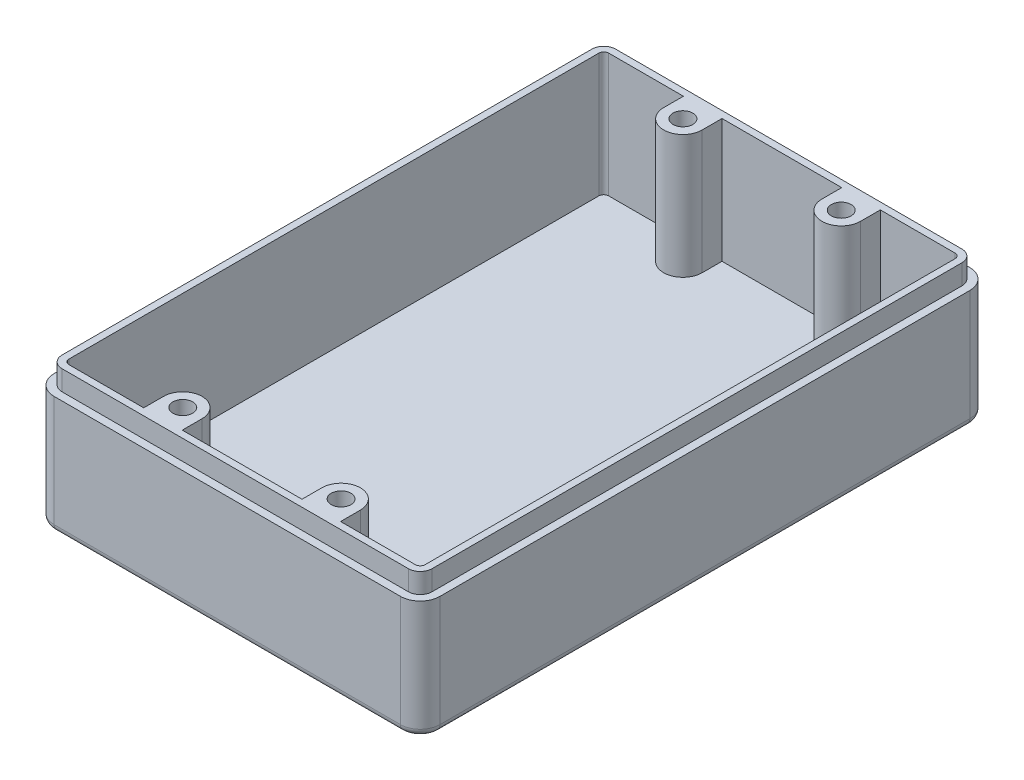
SolidWorks part; units mm, degrees
ref_plane "Plan de face" through (0, 0, 0) normal (0, 0, 1) x (1, 0, 0)
ref_plane "Plan de dessus" through (0, 0, 0) normal (0, 1, 0) x (1, 0, 0)
ref_plane "Plan de droite" through (0, 0, 0) normal (1, 0, 0) x (0, 0, -1)
sketch "Esquisse1" plane through (0, 0, 0) normal (0, 1, 0) x (1, 0, 0)
  line L1 (-39, 0) -> (39, 0)
  line L2 (-39, 0) -> (-39, 115.1)
  line L3 (-39, 115.1) -> (39, 115.1)
  line L4 (39, 0) -> (39, 115.1)
  dimension "D1" = 78
  dimension "D2" = 115.1
extrude "Top_Volume" add sketch "Esquisse1" along normal blind 28
fillet "Corner_Radius" radius 4 4 edges at (-39, 14, -115.1) (39, 14, -115.1) (39, 14, 0) (-39, 14, 0)
shell "Inside_Hole" thickness 3 removed face at (0, 28, -57.55)
sketch "Esquisse2" plane through (0, 28, 0) normal (0, 1, 0) x (1, 0, 0)
  line L8 (35, 113.5) -> (-35, 113.5)
  line L9 (-37.4, 111.1) -> (-37.4, 4)
  line L10 (-35, 1.6) -> (35, 1.6)
  line L11 (37.4, 4) -> (37.4, 111.1)
  line L12 (35, 113.5) -> (-35, 113.5)
  line L13 (-37.4, 111.1) -> (-37.4, 4)
  line L14 (-35, 1.6) -> (35, 1.6)
  line L15 (37.4, 4) -> (37.4, 111.1)
  arc A8 (-35, 113.5) -> (-37.4, 111.1) centre (-35, 111.1) ccw
  arc A9 (-35, 113.5) -> (-37.4, 111.1) centre (-35, 111.1) ccw
  arc A10 (-37.4, 4) -> (-35, 1.6) centre (-35, 4) ccw
  arc A11 (-37.4, 4) -> (-35, 1.6) centre (-35, 4) ccw
  arc A12 (35, 1.6) -> (37.4, 4) centre (35, 4) ccw
  arc A13 (35, 1.6) -> (37.4, 4) centre (35, 4) ccw
  arc A14 (37.4, 111.1) -> (35, 113.5) centre (35, 111.1) ccw
  arc A15 (37.4, 111.1) -> (35, 113.5) centre (35, 111.1) ccw
  dimension "D1" = 1.6
extrude "Border_Notch" cut sketch "Esquisse2" against normal blind 4.05 flip side to cut
sketch "Esquisse3" plane through (0, 3, 0) normal (0, 1, 0) x (1, 0, 0)
  line L0 (-19.9, 3) -> (-19.9, 7)
  line L1 (-35, 3) -> (35, 3) construction
  line L2 (-19.9, 3) -> (-12.1, 3)
  line L3 (-12.1, 3) -> (-12.1, 7)
  line L4 (-19.9, 7) -> (-12.1, 7) construction
  line L5 (-36, 57.55) -> (36, 57.55) construction
  line L6 (-36, 111.1) -> (-36, 4) construction
  line L7 (36, 4) -> (36, 111.1) construction
  line L8 (-19.9, 112.1) -> (-12.1, 112.1)
  line L9 (-19.9, 112.1) -> (-19.9, 108.1)
  line L10 (-12.1, 112.1) -> (-12.1, 108.1)
  arc A0 (-19.9, 7) -> (-12.1, 7) centre (-16, 7) cw
  circle A2 centre (-16, 7) radius 2
  circle A3 centre (-16, 108.1) radius 2
  arc A4 (-19.9, 108.1) -> (-12.1, 108.1) centre (-16, 108.1) ccw
  dimension "D4" = 4
  dimension "D2" = 4
  dimension "D3" = 16
extrude "Fixation_Col" add sketch "Esquisse3" along normal blind 25
mirror "Symétrie2" about plane through (0, 0, 0) normal (1, 0, 0) of "Fixation_Col"
fillet "Congé2" radius 1.5 8 edges at (-37.8284, 0, -1.1716) (0, 0, 0) (37.8284, 0, -1.1716) (39, 0, -57.55) (37.8284, 0, -113.9284) (0, 0, -115.1) (-37.8284, 0, -113.9284) (-39, 0, -57.55)
sketch "Esquisse4" plane through (0, 0, 0) normal (0, -1, 0) x (1, 0, 0)
  line L0 (-37.5, -4) -> (-37.5, -57.55) construction
  line L1 (-37.5, -4) -> (-37.5, -111.1) construction
  line L2 (-37.5, -57.55) -> (37.5, -57.55) construction
  line L3 (37.5, -111.1) -> (37.5, -4) construction
  line L4 (37.5, -57.55) -> (37.5, -4) construction
  line L5 (37.5, -4) -> (-37.5, -4) construction
  line L6 (-37.5, -57.55) -> (-37.5, -111.1) construction
  line L7 (-37.5, -111.1) -> (37.5, -111.1) construction
  line L8 (37.5, -111.1) -> (37.5, -57.55) construction
  line L9 (-37.5, -84.325) -> (37.5, -84.325) construction
  line L10 (-37.5, -30.775) -> (37.5, -30.775) construction
  text T0 "<b>ETML-ES</b>\r\n<b>SLO2-23</b>" font "Century Gothic" height 8
  text T1 "2228 Alarme fenêtre V1" font "Century Gothic" height 4
  text T2 "\r\nMiguel Santos" font "Century Gothic" height 6
extrude "Enlèv. mat.-Extru.2" cut sketch "Esquisse4" against normal blind 0.4
equation "\"PCB_Length_Y\"= 60mm"
equation "\"PCB_Width_X\"= 60mm"
equation "\"PCB_Thickness_Z\"= 1.55mm"
equation "\"PCB_Pos_Y\"= 5mm"
equation "\"PCB_Zone_Y\"= \"PCB_Length_Y\" + \"Box_Wall_Thickness\" 'Zone occupée par le PCB centrée au milieu de la zone"
equation "\"PCB_Zone_X\"= \"PCB_Width_X\" + 12mm"
equation "\"Battery_Zone_Y\"= \"Battery_Length_Y\" + \"Box_Wall_Thickness\" + \"Fixation_holes_offset\" + \"Col_Diameter\"/2 + \"Battery_Offset\" + \"Global_Gap\"*2"
equation "\"Battery_Length_Y\"= 25mm"
equation "\"Battery_Width_X\"= 55mm"
equation "\"Box_Wall_Thickness\"= 3mm"
equation "\"Box_Border_Height\"= \"Col_Height\" + \"PCB_Thickness_Z\""
equation "\"Box_Corner_Radius\"= 4mm"
equation "\"PCB_Holes_X\"= 52mm"
equation "\"PCB_Holes_Y\"= 52mm"
equation "\"Col_Height\"= 2.5mm"
equation "\"Box_Bottom_Thick\"= 3mm"
equation "\"Box_Top_Thick\"= 3mm"
equation "\"PCB_Components_Height\"= 22mm"
equation "\"Global_Gap\"= 0.1mm"
equation "\"Col_Diameter\"= 7.8mm"
equation "\"D1@Esquisse1\"=\"PCB_Zone_X\"+2 * \"Box_Wall_Thickness\""
equation "\"D2@Esquisse1\"=2 * \"Box_Wall_Thickness\" + \"PCB_Zone_Y\" + \"Battery_Zone_Y\""
equation "\"Inserts_Diameter\"= 4mm"
equation "\"Inserts_Height\"= 4mm"
equation "\"Fixation_holes_X\"= 32mm"
equation "\"Fixation_holes_offset\"= 4mm'Distance from inside border of hole center"
equation "\"Solar_Width_X\"= 23.4mm"
equation "\"Solar_Length_Y\"= 8.4mm"
equation "\"D1@Corner_Radius\" = \"Box_Corner_Radius\""
equation "\"D1@Inside_Hole\"=\"Box_Wall_Thickness\""
equation "\"D2@Inside_Hole\"= \"Box_Bottom_Thick\""
equation "\"D1@Border_Notch\" = \"Box_Border_Height\""
equation "\"D1@Esquisse2\"=\"Box_Wall_Thickness\"/2 + \"Global_Gap\""
equation "\"D1@Fixation_Col\"= \"PCB_Components_Height\""
equation "\"D3@Esquisse3\"=(\"PCB_Zone_Y\" - \"PCB_Holes_Y\")/2 + \"Box_Wall_Thickness\""
equation "\"D4@Esquisse3\"=\"Inserts_Diameter\""
equation "\"D1@Congé2\"=\"Box_Bottom_Thick\"/2"
equation "\"D1@Top_Volume\"=\"Box_Top_Thick\"+\"PCB_Components_Height\""
equation "\"D1@Enlèv. mat.-Extru.2\"=0.4mm"
equation "\"PCB_Components_Height\"= 25mm"
equation "\"D1@Esquisse3\"=\"Col_Diameter\""
equation "\"D2@Esquisse3\"=\"Fixation_holes_offset\""
equation "\"D3@Esquisse3\"=\"Fixation_holes_X\" / 2"
equation "\"Battery_Offset\"= 10mm"
